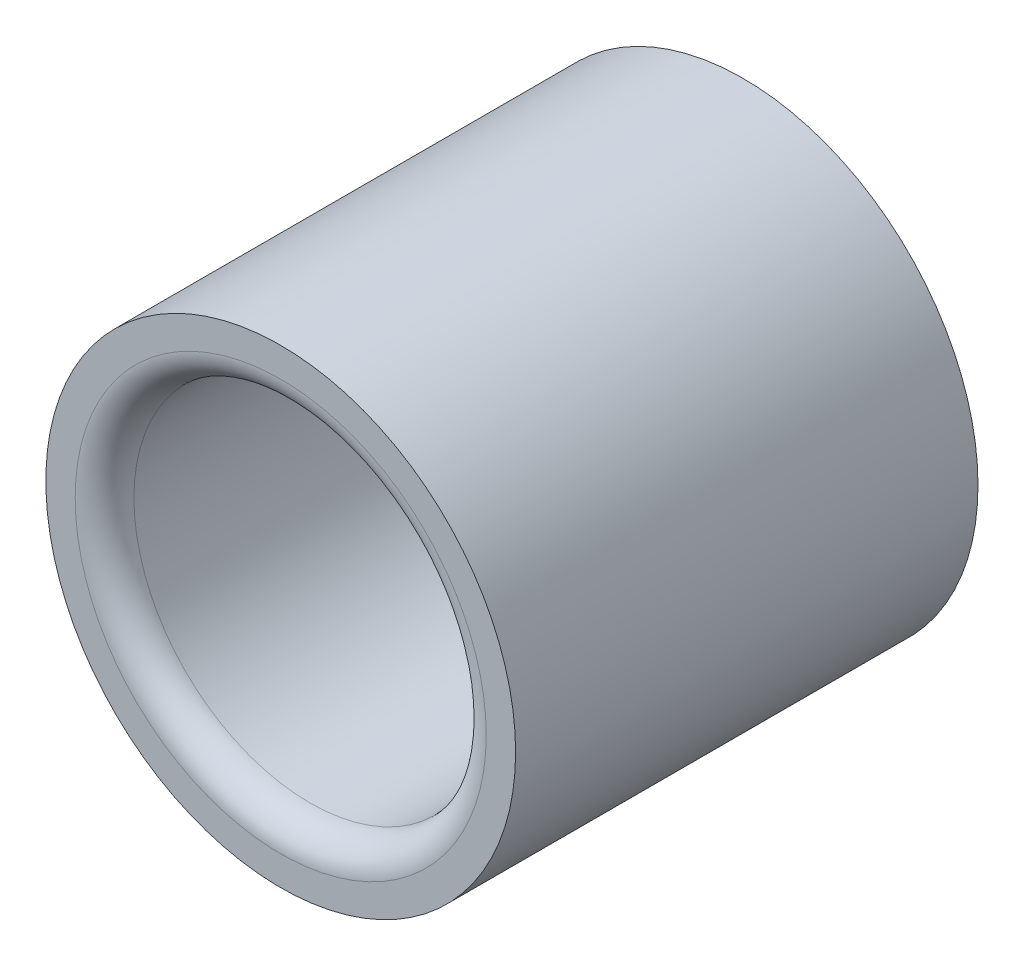
SolidWorks part; units mm, degrees
ref_plane "XY" through (0, 0, 0) normal (0, 0, 1) x (1, 0, 0)
ref_plane "XZ" through (0, 0, 0) normal (0, 1, 0) x (1, 0, 0)
ref_plane "YZ" through (0, 0, 0) normal (1, 0, 0) x (0, 0, -1)
ref_axis "X" through (-1.7463, 0, 0) along (1, 0, 0)
ref_axis "Y" through (0, -1.7463, 0) along (0, 1, 0)
ref_axis "Z" through (0, 0, 2.625) along (0, 0, -1)
sketch "Sketch1" plane through (0, 0, 0) normal (0, 0, 1) x (1, 0, 0)
  circle A0 centre (0, 0) radius 0.9525
  circle A1 centre (0, 0) radius 1.27
  point P5 (0, 0)
  point P6 (0.0624, 0)
  dimension "D1" = 2.54
  dimension "D2" = 1.905
extrude "Boss-Extrude1" add sketch "Sketch1" along normal blind 2.5
fillet "Fillet3" radius 0.1588 2 edges at (0.9525, 0, 2.5) (0.9525, 0, 0)
